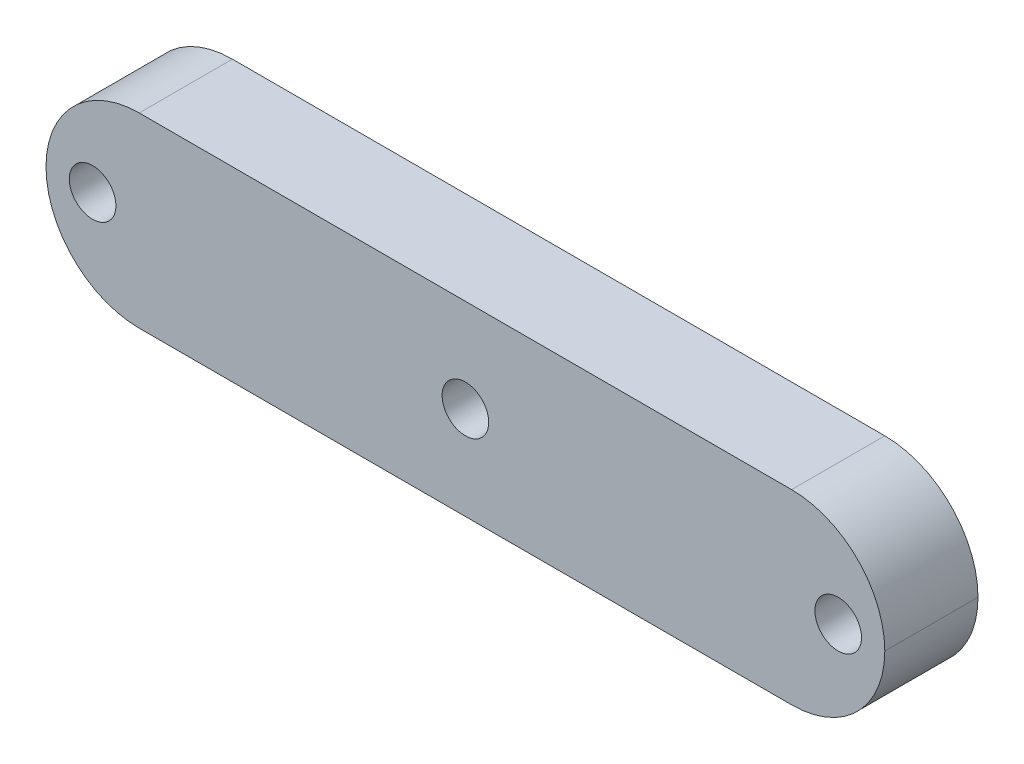
SolidWorks part; units mm, degrees
ref_plane "Front Plane" through (0, 0, 0) normal (0, 0, 1) x (1, 0, 0)
ref_plane "Top Plane" through (0, 0, 0) normal (0, 1, 0) x (1, 0, 0)
ref_plane "Right Plane" through (0, 0, 0) normal (1, 0, 0) x (0, 0, -1)
sketch "Sketch1" plane through (0, 0, 0) normal (0, 0, 1) x (1, 0, 0)
  line L1 (-45, 10) -> (45, 10)
  line L2 (-45, 10) -> (-45, -10)
  line L3 (-45, -10) -> (45, -10)
  line L4 (45, 10) -> (45, -10)
  line L5 (-45, 10) -> (45, -10) construction
  line L6 (-45, -10) -> (45, 10) construction
  circle A0 centre (-40, 0.1164) radius 2.5
  circle A1 centre (40, 0) radius 2.5
  circle A2 centre (0, 0) radius 2.5
  point P0 (0, 0)
  dimension "D4" = 5
  dimension "D5" = 5
  dimension "D6" = 5
  dimension "D7" = 5
  dimension "D1" = 90
  dimension "D2" = 20
  dimension "D3" = 5
  dimension "D9" = 10
extrude "Boss-Extrude1" add sketch "Sketch1" along normal blind 10
fillet "Fillet1" radius 10 4 edges at (45, -10, 5) (45, 10, 5) (-45, -10, 5) (-45, 10, 5)
